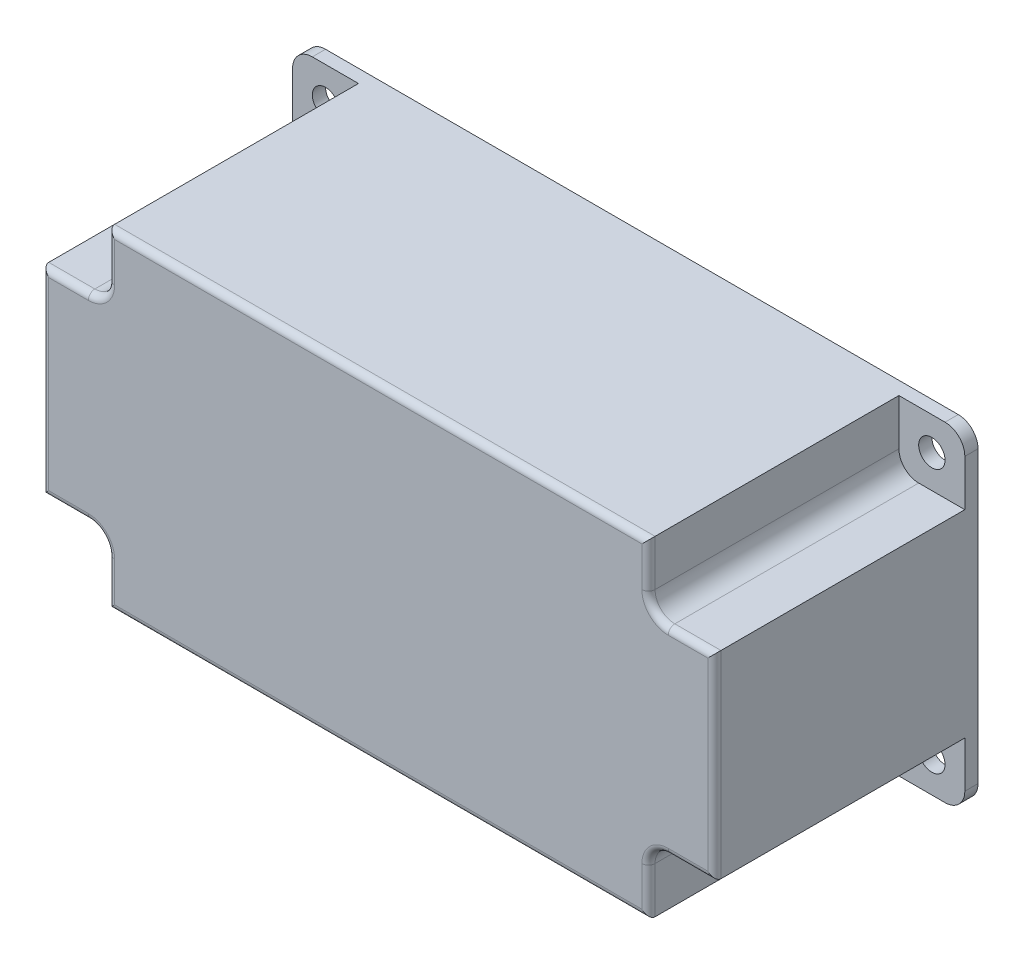
SolidWorks part; units mm, degrees
ref_plane "Alzado" through (0, 0, 0) normal (0, 0, 1) x (1, 0, 0)
ref_plane "Planta" through (0, 0, 0) normal (0, 1, 0) x (1, 0, 0)
ref_plane "Vista lateral" through (0, 0, 0) normal (1, 0, 0) x (0, 0, -1)
sketch "Croquis1" plane through (0, 0, 0) normal (0, 0, 1) x (1, 0, 0)
  line L1 (-51, 25) -> (51, 25)
  line L2 (-51, 25) -> (-51, -25)
  line L3 (-51, -25) -> (51, -25)
  line L4 (51, 25) -> (51, -25)
  line L5 (-51, 25) -> (51, -25) construction
  line L6 (-51, -25) -> (51, 25) construction
  point P0 (0, 0)
extrude "Saliente-Extruir1" add sketch "Croquis1" along normal blind 40
sketch "Croquis3" plane through (0, 0, 40) normal (0, 0, 1) x (1, 0, 0)
  line L0 (-51, -25) -> (-51, -15) construction
  line L1 (-51, 25) -> (-51, -25) construction
  line L2 (-51, -15) -> (-44, -15)
  line L3 (-41, -18) -> (-41, -25)
  line L4 (-51, -25) -> (51, -25) construction
  line L5 (-41, 25) -> (-41, 18)
  line L6 (51, 25) -> (-51, 25) construction
  line L7 (-51, 15) -> (-44, 15)
  line L8 (51, 15) -> (44, 15)
  line L9 (51, -25) -> (51, 25) construction
  line L10 (41, 25) -> (41, 18)
  line L11 (41, -25) -> (41, -18)
  line L12 (44, -15) -> (51, -15)
  line L14 (51, -25) -> (-51, -25)
  line L15 (51, -25) -> (51, 25)
  line L16 (51, 25) -> (-51, 25)
  line L17 (-51, -25) -> (-51, 25)
  line L18 (51, -25) -> (-51, 25) construction
  line L19 (51, 25) -> (-51, -25) construction
  arc A0 (44, 15) -> (41, 18) centre (44, 18) cw
  arc A1 (41, -18) -> (44, -15) centre (44, -18) cw
  arc A2 (-44, -15) -> (-41, -18) centre (-44, -18) cw
  arc A3 (-41, 18) -> (-44, 15) centre (-44, 18) cw
  point P21 (0, 0)
  point P30 (41, 15)
  point P35 (-41, -15)
  point P38 (-41, 15)
  line M14 (51, -25) -> (51, 25)
  line M15 (51, 25) -> (-51, 25)
  line M16 (-51, 25) -> (-51, -25)
  line M17 (-51, -25) -> (51, -25)
  dimension "D1" = 3
extrude "Cortar-Extruir1" cut sketch "Croquis3" against normal blind 38 contours A0 L8 L10 M14 M15 | A1 L11 L12 M17 M14 | A2 L2 L3 M16 M17 | A3 L5 L7 M15 M16 region at (-46.0853, -20.0853, 40) region at (-46.0853, 20.0853, 40) region at (46.0853, -20.0853, 40) region at (46.0853, 20.0853, 40)
sketch "Croquis4" plane through (0, 0, 2) normal (0, 0, 1) x (1, 0, 0)
  line L0 (-46, -20) -> (-51, -20) construction
  line L1 (-48, -25) -> (48, -25)
  line L2 (-51, -22) -> (-51, 22)
  line L3 (-48, 25) -> (48, 25)
  line L4 (51, -22) -> (51, 22)
  line L5 (-46, -25) -> (-46, -20) construction
  line L6 (51, -20) -> (46, -20) construction
  line L7 (46, 25) -> (46, 20) construction
  line L8 (-51, 20) -> (-46, 20) construction
  line L10 (-51, -25) -> (51, -25)
  line L11 (-51, -25) -> (-51, 25)
  line L12 (-51, 25) -> (51, 25)
  line L13 (51, -25) -> (51, 25)
  arc A0 (48, -25) -> (51, -22) centre (48, -22) ccw
  arc A1 (48, 25) -> (51, 22) centre (48, 22) cw
  arc A2 (-51, 22) -> (-48, 25) centre (-48, 22) cw
  arc A3 (-48, -25) -> (-51, -22) centre (-48, -22) cw
  circle A4 centre (-46, 20) radius 2
  circle A5 centre (-46, -20) radius 2
  circle A6 centre (46, -20) radius 2
  circle A7 centre (46, 20) radius 2
  point P10 (51, 25)
  point P15 (-51, -25)
  line M15 (-51, -15) -> (-51, -25)
  line M16 (-51, -25) -> (-41, -25)
  dimension "D1" = 3
extrude "Cortar-Extruir2" cut sketch "Croquis4" against normal blind 18 contours A3 M16 M15 | A5 | L11 A2 L12 | A4 | A7 | L12 A1 L13 | A6 | A0 L10 L13 region at (-50.3299, -24.3299, 2) region at (50.3299, -24.3299, 2) region at (-50.3299, 24.3299, 2) region at (50.3299, 24.3299, 2) region at (-46, 20, 2) region at (-46, -20, 2) region at (46, -20, 2) region at (46, 20, 2)
fillet "Redondeo1" radius 1 16 edges at (-41.8787, 15.8787, 40) (-41, 21.5, 40) (0, 25, 40) (41, 21.5, 40) (41.8787, 15.8787, 40) (47.5, 15, 40) (51, 0, 40) (47.5, -15, 40) (41.8787, -15.8787, 40) (41, -21.5, 40) (0, -25, 40) (-41, -21.5, 40) (-41.8787, -15.8787, 40) (-47.5, -15, 40) (-51, 0, 40) (-47.5, 15, 40)
sketch "Croquis5" plane through (0, 0, 0) normal (0, 0, -1) x (-1, 0, 0)
  line L0 (39.5, -15.4722) -> (39.5, -25) construction
  line L1 (51, -13.4722) -> (41.5, -13.4722) construction
  line L2 (51, 22) -> (51, -22) construction
  line L3 (48, -25) -> (-48, -25) construction
  line L4 (39.5, 25) -> (39.5, 15.5) construction
  line L5 (-48, 25) -> (48, 25) construction
  line L6 (51, 13.5) -> (41.5, 13.5) construction
  line L7 (-51, -13.4722) -> (-41.4905, -13.4722) construction
  line L8 (-51, -22) -> (-51, 22) construction
  line L9 (-39.4905, -25) -> (-39.4905, -15.4722) construction
  line L10 (-39.4905, 15.5) -> (-39.4905, 25) construction
  line L11 (-41.4905, 13.5) -> (-51, 13.5) construction
  line L12 (51, 0) -> (49.4746, 0) construction
  line L13 (0, -25) -> (0, -23.5) construction
  line L14 (-51, 0) -> (-49.5254, 0) construction
  line L15 (0, 25) -> (0, 23.5) construction
  line L16 (0, 23.5) -> (-39.4905, 23.5)
  line L17 (49.4746, 13.5) -> (49.4746, -13.4722)
  line L18 (49.4746, -13.4722) -> (41.5, -13.4722)
  line L19 (39.5, -15.4722) -> (39.5, -23.5)
  line L20 (39.5, -23.5) -> (-39.4905, -23.5)
  line L21 (-39.4905, -23.5) -> (-39.4905, -15.4722)
  line L22 (-41.4905, -13.4722) -> (-49.5254, -13.4722)
  line L23 (-49.5254, -13.4722) -> (-49.5254, 13.5)
  line L24 (-49.5254, 13.5) -> (-41.4905, 13.5)
  line L25 (-39.4905, 15.5) -> (-39.4905, 23.5)
  line L26 (49.4746, 13.5) -> (41.5, 13.5)
  line L27 (39.5, 15.5) -> (39.5, 23.5)
  line L28 (39.5, 23.5) -> (0, 23.5)
  line L29 (-51, -15.4722) -> (-39.4905, -15.4722) construction
  line L30 (-51, 15.5) -> (-39.4905, 15.5) construction
  line L31 (-41.4905, 25) -> (-41.4905, 13.5) construction
  line L32 (41.5, 25) -> (41.5, 13.5) construction
  line L33 (51, 15.5) -> (39.5, 15.5) construction
  line L34 (51, -15.4722) -> (39.5, -15.4722) construction
  line L35 (41.5, -25) -> (41.5, -13.5) construction
  line L36 (-41.4905, -25) -> (-41.4905, -13.4722) construction
  arc A0 (39.5, 15.5) -> (41.5, 13.5) centre (41.5, 15.5) ccw
  arc A1 (41.5, -13.4722) -> (39.5, -15.4722) centre (41.5, -15.4722) ccw
  arc A2 (-41.4905, -13.4722) -> (-39.4905, -15.4722) centre (-41.4905, -15.4722) cw
  arc A3 (-39.4905, 15.5) -> (-41.4905, 13.5) centre (-41.4905, 15.5) cw
  point P34 (39.5, -13.4722)
  point P37 (-39.4905, -13.4722)
  dimension "D1" = 2
extrude "Cortar-Extruir3" cut sketch "Croquis5" against normal blind 38
sketch "Croquis6" plane through (-51, 0, 0) normal (-1, 0, 0) x (0, 0, 1)
  circle A0 centre (19.2286, 0) radius 10
extrude "Cortar-Extruir4" cut sketch "Croquis6" against normal blind 10
